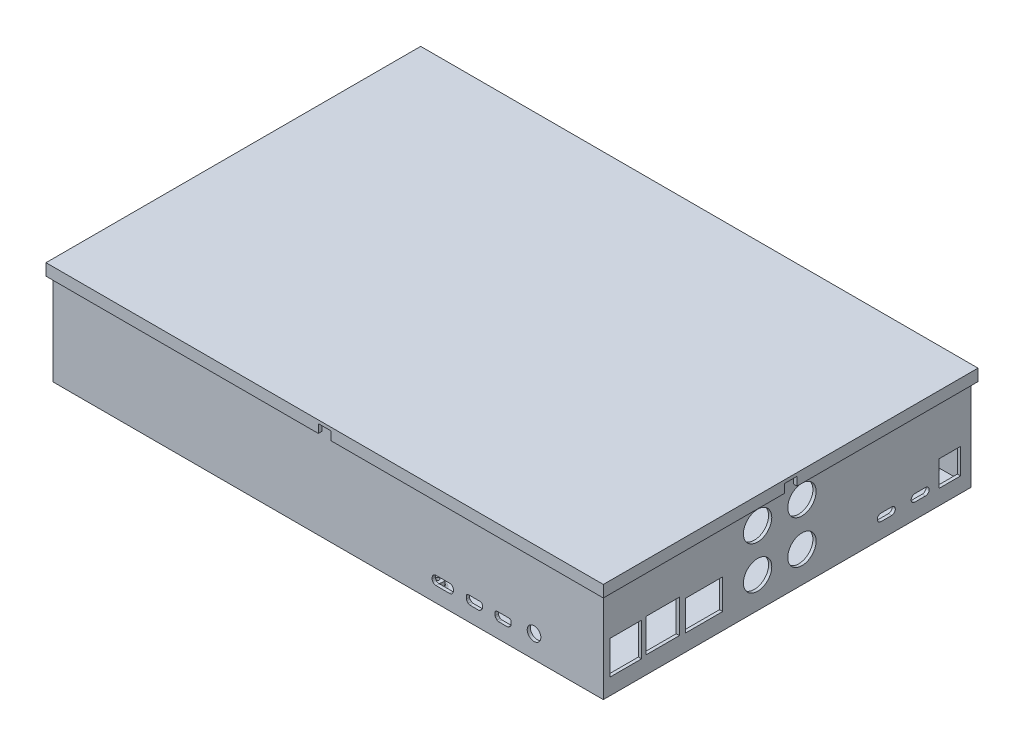
SolidWorks part; units mm, degrees
ref_plane "Front Plane" through (0, 0, 0) normal (0, 0, 1) x (1, 0, 0)
ref_plane "Top Plane" through (0, 0, 0) normal (0, 1, 0) x (1, 0, 0)
ref_plane "Right Plane" through (0, 0, 0) normal (1, 0, 0) x (0, 0, -1)
sketch "Sketch1" plane through (0, 0, 0) normal (0, -1, 0) x (1, 0, 0)
  line L0 (-24.0179, 95.5892) -> (-144.0179, 95.5892) construction
  line L1 (-174.0179, 95.5892) -> (80.9821, 95.5892)
  line L2 (-174.0179, 95.5892) -> (-174.0179, -73.7508)
  line L3 (-174.0179, -73.7508) -> (80.9821, -73.7508)
  line L4 (80.9821, 95.5892) -> (80.9821, -73.7508)
  line L5 (-24.0179, 95.5892) -> (-144.0179, 95.5892)
  line L6 (79.9821, -73.7508) -> (-17.0779, -73.7508) construction
  line L7 (79.9821, -73.7508) -> (-17.0779, -73.7508)
  line L8 (80.9821, -21.4108) -> (80.9821, -72.7508) construction
  line L9 (80.9821, -21.4108) -> (80.9821, -72.7508)
  line L10 (-144.0179, 95.5892) -> (-144.0179, 15.5892) construction
  line L11 (-144.0179, 95.5892) -> (-144.0179, 15.5892)
  dimension "D1" = 30
  dimension "D2" = 0
  dimension "D3" = 0
  dimension "D4" = 0
extrude "Boss-Extrude1" add sketch "Sketch1" along normal blind 2 from offset 4 contours L4 L3 L2 L1
sketch "Sketch2" plane through (0, -4, 0) normal (0, 1, 0) x (1, 0, 0)
  line L0 (-175.5179, 75.2508) -> (-175.5179, -97.0892)
  line L1 (-175.5179, -97.0892) -> (82.4821, -97.0892)
  line L2 (82.4821, -97.0892) -> (82.4821, 75.2508)
  line L3 (82.4821, 75.2508) -> (-175.5179, 75.2508)
  line L4 (-174.0179, -95.5892) -> (80.9821, -95.5892)
  line L5 (80.9821, -95.5892) -> (80.9821, 73.7508)
  line L6 (80.9821, 73.7508) -> (-174.0179, 73.7508)
  line L7 (-174.0179, 73.7508) -> (-174.0179, -95.5892)
  line L8 (-174.0179, -95.5892) -> (80.9821, -95.5892)
  line L9 (80.9821, -95.5892) -> (80.9821, 73.7508)
  line L10 (80.9821, 73.7508) -> (-174.0179, 73.7508)
  line L11 (-174.0179, 73.7508) -> (-174.0179, -95.5892)
  dimension "D1" = 0
  dimension "D2" = 1.5
extrude "Boss-Extrude2" add sketch "Sketch2" along normal blind 45 and the other way up to surface (2 mm away) other way up to face at (-46.5179, -6, 10.9192)
sketch "Sketch3" plane through (0, 0, 97.0892) normal (0, 0, 1) x (1, 0, 0)
  line L8 (4.0121, 1.1) -> (10.3521, 1.1)
  line L9 (12.1521, 2.9) -> (12.1521, 3.46)
  line L10 (10.3521, 5.26) -> (4.0121, 5.26)
  line L11 (2.2121, 3.46) -> (2.2121, 2.9)
  line L12 (4.0121, 1.1) -> (10.3521, 1.1)
  line L13 (12.1521, 2.9) -> (12.1521, 3.46)
  line L14 (10.3521, 5.26) -> (4.0121, 5.26)
  line L15 (2.2121, 3.46) -> (2.2121, 2.9)
  line L32 (21.8221, 1.1) -> (19.8266, 1.1)
  line L33 (19.1371, 1.3964) -> (18.4927, 2.0762)
  line L34 (18.2321, 2.7298) -> (18.2321, 4.05)
  line L35 (19.1821, 5) -> (24.7821, 5)
  line L36 (21.8221, 1.1) -> (19.8266, 1.1)
  line L37 (19.1371, 1.3964) -> (18.4927, 2.0762)
  line L38 (18.2321, 2.7298) -> (18.2321, 4.05)
  line L39 (19.1821, 5) -> (24.7821, 5)
  line L54 (22.1421, 1.1) -> (24.1376, 1.1)
  line L55 (24.827, 1.3964) -> (25.4715, 2.0762)
  line L56 (25.7321, 2.7298) -> (25.7321, 4.05)
  line L57 (22.1421, 1.1) -> (24.1376, 1.1)
  line L58 (24.827, 1.3964) -> (25.4715, 2.0762)
  line L59 (25.7321, 2.7298) -> (25.7321, 4.05)
  line L86 (35.6421, 1.1) -> (35.3221, 1.1)
  line L87 (39.2321, 4.05) -> (39.2321, 2.7298)
  line L88 (35.3221, 1.1) -> (33.3266, 1.1)
  line L89 (32.6371, 1.3964) -> (31.9927, 2.0762)
  line L90 (31.7321, 2.7298) -> (31.7321, 4.05)
  line L91 (32.6821, 5) -> (38.2821, 5)
  line L92 (39.2321, 4.05) -> (39.2321, 2.7298)
  line L93 (35.3221, 1.1) -> (33.3266, 1.1)
  line L94 (32.6371, 1.3964) -> (31.9927, 2.0762)
  line L95 (31.7321, 2.7298) -> (31.7321, 4.05)
  line L96 (32.6821, 5) -> (38.2821, 5)
  line L97 (22.1421, 1.1) -> (21.8221, 1.1)
  line L98 (35.6421, 1.1) -> (37.6376, 1.1)
  line L99 (38.327, 1.3964) -> (38.9715, 2.0762)
  line L100 (35.6421, 1.1) -> (37.6376, 1.1)
  line L101 (38.327, 1.3964) -> (38.9715, 2.0762)
  arc A8 (10.3521, 1.1) -> (12.1521, 2.9) centre (10.3521, 2.9) ccw
  arc A9 (12.1521, 3.46) -> (10.3521, 5.26) centre (10.3521, 3.46) ccw
  arc A10 (4.0121, 5.26) -> (2.2121, 3.46) centre (4.0121, 3.46) ccw
  arc A11 (2.2121, 2.9) -> (4.0121, 1.1) centre (4.0121, 2.9) ccw
  arc A12 (10.3521, 1.1) -> (12.1521, 2.9) centre (10.3521, 2.9) ccw
  arc A13 (12.1521, 3.46) -> (10.3521, 5.26) centre (10.3521, 3.46) ccw
  arc A14 (4.0121, 5.26) -> (2.2121, 3.46) centre (4.0121, 3.46) ccw
  arc A15 (2.2121, 2.9) -> (4.0121, 1.1) centre (4.0121, 2.9) ccw
  arc A27 (19.1371, 1.3964) -> (19.8266, 1.1) centre (19.8266, 2.05) ccw
  arc A28 (18.2321, 2.7298) -> (18.4927, 2.0762) centre (19.1821, 2.7298) ccw
  arc A29 (19.1821, 5) -> (18.2321, 4.05) centre (19.1821, 4.05) ccw
  arc A30 (19.1371, 1.3964) -> (19.8266, 1.1) centre (19.8266, 2.05) ccw
  arc A31 (18.2321, 2.7298) -> (18.4927, 2.0762) centre (19.1821, 2.7298) ccw
  arc A32 (19.1821, 5) -> (18.2321, 4.05) centre (19.1821, 4.05) ccw
  arc A53 (24.1376, 1.1) -> (24.827, 1.3964) centre (24.1376, 2.05) ccw
  arc A54 (25.4715, 2.0762) -> (25.7321, 2.7298) centre (24.7821, 2.7298) ccw
  arc A55 (25.7321, 4.05) -> (24.7821, 5) centre (24.7821, 4.05) ccw
  arc A56 (24.1376, 1.1) -> (24.827, 1.3964) centre (24.1376, 2.05) ccw
  arc A57 (25.4715, 2.0762) -> (25.7321, 2.7298) centre (24.7821, 2.7298) ccw
  arc A58 (25.7321, 4.05) -> (24.7821, 5) centre (24.7821, 4.05) ccw
  arc A80 (39.2321, 4.05) -> (38.2821, 5) centre (38.2821, 4.05) ccw
  arc A81 (32.6371, 1.3964) -> (33.3266, 1.1) centre (33.3266, 2.05) ccw
  arc A82 (31.7321, 2.7298) -> (31.9927, 2.0762) centre (32.6821, 2.7298) ccw
  arc A83 (32.6821, 5) -> (31.7321, 4.05) centre (32.6821, 4.05) ccw
  arc A84 (39.2321, 4.05) -> (38.2821, 5) centre (38.2821, 4.05) ccw
  arc A85 (32.6371, 1.3964) -> (33.3266, 1.1) centre (33.3266, 2.05) ccw
  arc A86 (31.7321, 2.7298) -> (31.9927, 2.0762) centre (32.6821, 2.7298) ccw
  arc A87 (32.6821, 5) -> (31.7321, 4.05) centre (32.6821, 4.05) ccw
  arc A92 (37.6376, 1.1) -> (38.327, 1.3964) centre (37.6376, 2.05) ccw
  arc A93 (38.9715, 2.0762) -> (39.2321, 2.7298) centre (38.2821, 2.7298) ccw
  arc A94 (37.6376, 1.1) -> (38.327, 1.3964) centre (37.6376, 2.05) ccw
  arc A95 (38.9715, 2.0762) -> (39.2321, 2.7298) centre (38.2821, 2.7298) ccw
  circle A96 centre (49.9821, 4.6) radius 3.2
  circle A97 centre (49.9821, 4.6) radius 3.2
  dimension "D1" = 0.5
  dimension "D2" = 0.5
  dimension "D3" = 0.5
  dimension "D4" = 0.5
  dimension "D5" = 0.5
  dimension "D6" = 0.5
extrude "Cut-Extrude1" cut sketch "Sketch3" against normal blind 30
sketch "Sketch4" plane through (82.4821, 0, 0) normal (1, 0, 0) x (0, 0, -1)
  line L0 (38.5008, 4.145) -> (32.8008, 4.145) construction
  line L1 (38.5008, 4.145) -> (32.8008, 4.145)
  line L2 (48.6758, 4.0894) -> (54.3758, 4.0894) construction
  line L3 (48.6758, 4.0894) -> (54.3758, 4.0894)
  line L4 (38.5008, 4.145) -> (48.6758, 4.0894)
  line L5 (43.5883, 4.1172) -> (43.5883, 5.0147)
  line L6 (35.6508, 4.145) -> (35.6508, 1.7159)
  line L7 (51.5258, 4.0894) -> (51.5258, 1.7512)
  line L8 (49.0258, 2.9203) -> (54.0258, 2.9203) construction
  line L9 (49.0258, 4.645) -> (54.0258, 4.645)
  line L10 (49.0258, 1.1956) -> (54.0258, 1.1956)
  line L11 (38.1508, 2.9203) -> (33.1508, 2.9203) construction
  line L12 (38.1508, 4.645) -> (33.1508, 4.645)
  line L13 (38.1508, 1.1956) -> (33.1508, 1.1956)
  line L22 (70.4488, 13.1) -> (60.4488, 13.1)
  line L23 (60.4488, 13.1) -> (60.4488, 1.1)
  line L24 (60.4488, 1.1) -> (70.4488, 1.1)
  line L25 (70.4488, 1.1) -> (70.4488, 13.1)
  line L26 (70.4488, 13.1) -> (60.4488, 13.1)
  line L27 (60.4488, 13.1) -> (60.4488, 1.1)
  line L28 (60.4488, 1.1) -> (70.4488, 1.1)
  line L29 (70.4488, 1.1) -> (70.4488, 13.1)
  arc A0 (49.0258, 4.645) -> (49.0258, 1.1956) centre (49.0258, 2.9203) ccw
  arc A1 (54.0258, 1.1956) -> (54.0258, 4.645) centre (54.0258, 2.9203) ccw
  arc A2 (38.1508, 4.645) -> (38.1508, 1.1956) centre (38.1508, 2.9203) cw
  arc A3 (33.1508, 1.1956) -> (33.1508, 4.645) centre (33.1508, 2.9203) cw
  point P12 (51.5258, 2.9203)
  point P19 (35.6508, 2.9203)
  dimension "D1" = 5
  dimension "D2" = 0.5
extrude "Cut-Extrude2" cut sketch "Sketch4" against normal blind 30 contours A3 L13 A2 L12 | L10 A1 L9 A0 | L28 L29 L26 L27 region at (82.4821, 4.4177, -48.3732) region at (82.4821, 2.2955, -39.66) region at (82.4821, 7.1, -65.4488)
sketch "Sketch5" plane through (82.4821, 0, 0) normal (1, 0, 0) x (0, 0, -1)
  line L8 (-76.9733, 17.8) -> (-61.4142, 17.8)
  line L9 (-76.9733, 17.8) -> (-76.9733, 2.18)
  line L10 (-58.5892, 15.9) -> (-58.5892, 1.8)
  line L11 (-41.0892, 15.9) -> (-58.5892, 15.9)
  line L12 (-41.0892, 1.8) -> (-41.0892, 15.9)
  line L13 (-58.5892, 15.9) -> (-58.5892, 1.8)
  line L14 (-41.0892, 15.9) -> (-58.5892, 15.9)
  line L15 (-41.0892, 1.8) -> (-41.0892, 15.9)
  line L16 (-76.9733, 2.18) -> (-61.4142, 2.18)
  line L17 (-61.4142, 17.8) -> (-61.4142, 2.18)
  line L18 (-68.5792, 2.18) -> (-63.3392, 2.18) construction
  line L19 (-63.3392, 17.8) -> (-73.8392, 17.8) construction
  line L20 (-94.0392, 11) -> (-94.0392, 8.6) construction
  line L21 (-94.0392, 17.32) -> (-79.1392, 17.32)
  line L22 (-94.0392, 17.32) -> (-94.0392, 1.6)
  line L23 (-94.0392, 1.6) -> (-79.1392, 1.6)
  line L24 (-79.1392, 17.32) -> (-79.1392, 1.6)
  line L26 (-94.0392, 7.3258) -> (-94.0392, 7.2852)
  line L28 (-94.5261, 7.3258) -> (-94.5261, 7.2852)
  line L29 (-79.1392, 11) -> (-79.1392, 8.6) construction
  line L30 (-92.5892, 1.6) -> (-42.5892, 1.6) construction
  line L31 (-83.8392, 17.32) -> (-86.5392, 17.32) construction
  line L32 (-41.0892, 1.8) -> (-58.5892, 1.8)
  arc A2 (-3.9298, 3.1042) -> (-3.9298, 13.9042) centre (-3.9298, 8.5042) ccw construction
  arc A3 (-3.9298, 3.1042) -> (-3.9298, 13.9042) centre (-3.9298, 8.5042) ccw
  arc A4 (-3.9298, 35.3458) -> (-3.9298, 22.0458) centre (-3.9298, 28.6958) ccw
  arc A5 (-3.9298, 22.0458) -> (-3.9298, 35.3458) centre (-3.9298, 28.6958) ccw
  arc A6 (-3.9298, 35.3458) -> (-3.9298, 22.0458) centre (-3.9298, 28.6958) ccw
  arc A7 (-3.9298, 22.0458) -> (-3.9298, 35.3458) centre (-3.9298, 28.6958) ccw
  arc A8 (-24.7298, 3.1042) -> (-24.7298, 13.9042) centre (-24.7298, 8.5042) ccw construction
  arc A9 (-24.7298, 3.1042) -> (-24.7298, 13.9042) centre (-24.7298, 8.5042) ccw
  circle A10 centre (-24.7298, 28.5042) radius 6.65
  circle A11 centre (-24.7298, 8.5042) radius 6.65
  circle A12 centre (-3.9298, 8.5042) radius 6.65
  spline S0 degree 3 poles (-711.4769, 4971.8053) (-337.5237, 1657.2751) (-108.2325, 7.3404) (-23.5785, 22.0054) (-23.5551, 22.0096) (-23.1608, 22.0825) (-22.8013, 22.1812) (-22.4001, 22.3289) (-22.3521, 22.3471) (-21.9895, 22.4907) (-21.6902, 22.6363) (-21.3063, 22.8605) (-21.2135, 22.9178) (-20.7371, 23.2292) (-20.3848, 23.5154) (-19.7811, 24.119) (-19.5272, 24.4235) (-19.2685, 24.7977) (-19.2361, 24.846) (-18.9769, 25.2424) (-18.7832, 25.6106) (-18.6139, 26.023) (-18.603, 26.05) (-18.4455, 26.4477) (-18.3328, 26.8309) (-18.2499, 27.2507) (-18.2445, 27.2785) (-18.1665, 27.6999) (-18.1298, 28.1009) (-18.1297, 28.8824) (-18.162, 29.2579) (-18.2309, 29.6555) (-18.2351, 29.6789) (-18.308, 30.0732) (-18.4067, 30.4328) (-18.5544, 30.8339) (-18.5727, 30.8819) (-18.7162, 31.2445) (-18.8618, 31.5439) (-19.086, 31.9277) (-19.1433, 32.0206) (-19.4547, 32.4969) (-19.741, 32.8492) (-20.3445, 33.4529) (-20.6491, 33.7069) (-21.0232, 33.9655) (-21.0716, 33.9979) (-21.4679, 34.2571) (-21.8361, 34.4508) (-22.2485, 34.6202) (-22.2755, 34.631) (-22.6732, 34.7885) (-23.0564, 34.9012) (-23.4762, 34.9842) (-23.504, 34.9895) (-76.1673, 44.7393) (-206.8261, -591.9511) (4537.529, -1875.475) knots -6.623505 -6.623505 -6.623505 -6.623505 0.029297 0.029297 0.03125 0.03125 0.058594 0.058594 0.0625 0.0625 0.085938 0.085938 0.09375 0.09375 0.125 0.125 0.152344 0.152344 0.15625 0.15625 0.185547 0.185547 0.1875 0.1875 0.216797 0.216797 0.21875 0.21875 0.25 0.25 0.279297 0.279297 0.28125 0.28125 0.308594 0.308594 0.3125 0.3125 0.335938 0.335938 0.34375 0.34375 0.375 0.375 0.402344 0.402344 0.40625 0.40625 0.435547 0.435547 0.4375 0.4375 0.466797 0.466797 0.46875 0.46875 4.61643 4.61643 4.61643 4.61643 weights 1 1 1 1 1 1 1 1 1 1 1 1 1 1 1 1 1 1 1 1 1 1 1 1 1 1 1 1 1 1 1 1 1 1 1 1 1 1 1 1 1 1 1 1 1 1 1 1 1 1 1 1 1 1 1 1 1 1 only from (-24.7298, 21.9042) to (-24.7298, 35.1042) construction
  spline S1 degree 3 poles (-24.7298, 21.9042) (-24.3515, 21.9042) (-23.976, 21.9365) (-23.5785, 22.0054) (-23.5551, 22.0096) (-23.1608, 22.0825) (-22.8013, 22.1812) (-22.4001, 22.3289) (-22.3521, 22.3471) (-21.9895, 22.4907) (-21.6902, 22.6363) (-21.3063, 22.8605) (-21.2135, 22.9178) (-20.7371, 23.2292) (-20.3848, 23.5154) (-19.7811, 24.119) (-19.5272, 24.4235) (-19.2685, 24.7977) (-19.2361, 24.846) (-18.9769, 25.2424) (-18.7832, 25.6106) (-18.6139, 26.023) (-18.603, 26.05) (-18.4455, 26.4477) (-18.3328, 26.8309) (-18.2499, 27.2507) (-18.2445, 27.2785) (-18.1665, 27.6999) (-18.1298, 28.1009) (-18.1297, 28.8824) (-18.162, 29.2579) (-18.2309, 29.6555) (-18.2351, 29.6789) (-18.308, 30.0732) (-18.4067, 30.4328) (-18.5544, 30.8339) (-18.5727, 30.8819) (-18.7162, 31.2445) (-18.8618, 31.5439) (-19.086, 31.9277) (-19.1433, 32.0206) (-19.4547, 32.4969) (-19.741, 32.8492) (-20.3445, 33.4529) (-20.6491, 33.7069) (-21.0232, 33.9655) (-21.0716, 33.9979) (-21.4679, 34.2571) (-21.8361, 34.4508) (-22.2485, 34.6202) (-22.2755, 34.631) (-22.6732, 34.7885) (-23.0564, 34.9012) (-23.4762, 34.9842) (-23.504, 34.9895) (-23.9254, 35.0675) (-24.3264, 35.1042) (-24.7298, 35.1042) knots 0 0 0 0 0.029297 0.029297 0.03125 0.03125 0.058594 0.058594 0.0625 0.0625 0.085938 0.085938 0.09375 0.09375 0.125 0.125 0.152344 0.152344 0.15625 0.15625 0.185547 0.185547 0.1875 0.1875 0.216797 0.216797 0.21875 0.21875 0.25 0.25 0.279297 0.279297 0.28125 0.28125 0.308594 0.308594 0.3125 0.3125 0.335938 0.335938 0.34375 0.34375 0.375 0.375 0.402344 0.402344 0.40625 0.40625 0.435547 0.435547 0.4375 0.4375 0.466797 0.466797 0.46875 0.46875 0.5 0.5 0.5 0.5 weights 1 1 1 1 1 1 1 1 1 1 1 1 1 1 1 1 1 1 1 1 1 1 1 1 1 1 1 1 1 1 1 1 1 1 1 1 1 1 1 1 1 1 1 1 1 1 1 1 1 1 1 1 1 1 1 1 1 1
  dimension "D2" = 6.65
  dimension "D1" = 0.5
  dimension "D3" = 1
extrude "Cut-Extrude4" cut sketch "Sketch5" against normal blind 30 contours A10 | A11 | A12 | A6 A7 | L32 L15 L14 L13 | L17 L8 L9 L16 | L24 L21 L22 L23 region at (82.4821, 9.99, 69.1938) region at (82.4821, 8.85, 49.8392) region at (82.4821, 9.46, 86.5892) region at (82.4821, 28.6958, 3.9298) region at (82.4821, 28.5042, 24.7298) region at (82.4821, 8.5042, 24.7298) region at (82.4821, 8.5042, 3.9298)
sketch "Sketch6" plane through (-174.0179, 0, 0) normal (1, 0, 0) x (0, 0, -1)
  line L0 (-54.3892, 12.7658) -> (-54.3892, 24.6258)
  line L1 (-28.353, 19.2474) -> (-28.861, 19.7554)
  line L2 (-25.813, 19.2474) -> (-26.321, 19.7554)
  line L3 (-13.059, 19.7554) -> (-12.551, 19.2474)
  line L4 (-15.091, 19.2474) -> (-15.599, 19.7554)
  line L5 (-12.551, 19.2474) -> (-12.551, 19.7554)
  line L6 (-12.551, 19.7554) -> (-13.059, 19.7554)
  line L7 (-13.059, 19.7554) -> (-13.059, 19.2474)
  line L8 (-13.059, 19.2474) -> (-12.551, 19.2474)
  line L9 (-12.551, 19.2474) -> (-12.551, 19.7554)
  line L10 (-12.551, 19.7554) -> (-13.059, 19.7554)
  line L11 (-13.059, 19.7554) -> (-13.059, 19.2474)
  line L12 (-13.059, 19.2474) -> (-12.551, 19.2474)
  line L13 (-15.599, 19.7554) -> (-15.599, 19.2474)
  line L14 (-15.599, 19.2474) -> (-15.091, 19.2474)
  line L15 (-15.091, 19.2474) -> (-15.091, 19.7554)
  line L16 (-15.091, 19.7554) -> (-15.599, 19.7554)
  line L17 (-15.599, 19.7554) -> (-15.599, 19.2474)
  line L18 (-15.599, 19.2474) -> (-15.091, 19.2474)
  line L19 (-15.091, 19.2474) -> (-15.091, 19.7554)
  line L20 (-15.091, 19.7554) -> (-15.599, 19.7554)
  line L21 (-25.813, 19.2474) -> (-25.813, 19.7554)
  line L22 (-25.813, 19.7554) -> (-26.321, 19.7554)
  line L23 (-26.321, 19.7554) -> (-26.321, 19.2474)
  line L24 (-26.321, 19.2474) -> (-25.813, 19.2474)
  line L25 (-25.813, 19.2474) -> (-25.813, 19.7554)
  line L26 (-25.813, 19.7554) -> (-26.321, 19.7554)
  line L27 (-26.321, 19.7554) -> (-26.321, 19.2474)
  line L28 (-26.321, 19.2474) -> (-25.813, 19.2474)
  line L29 (-28.861, 19.7554) -> (-28.861, 19.2474)
  line L30 (-28.861, 19.2474) -> (-28.353, 19.2474)
  line L31 (-28.353, 19.2474) -> (-28.353, 19.7554)
  line L32 (-28.353, 19.7554) -> (-28.861, 19.7554)
  line L33 (-28.861, 19.7554) -> (-28.861, 19.2474)
  line L34 (-28.861, 19.2474) -> (-28.353, 19.2474)
  line L35 (-28.353, 19.2474) -> (-28.353, 19.7554)
  line L36 (-28.353, 19.7554) -> (-28.861, 19.7554)
  circle A0 centre (-54.3892, 18.6958) radius 6.65
  circle A1 centre (-75.1892, 18.6958) radius 6.65
  arc A2 (-75.1892, 16.1958) -> (-75.1892, 21.1958) centre (-75.1892, 18.6958) ccw construction
  arc A3 (-75.1892, 16.1958) -> (-75.1892, 21.1958) centre (-75.1892, 18.6958) ccw
  circle A5 centre (51.6265, 20.5) radius 8.75 construction
  arc A6 (21.8151, 16.0167) -> (21.8555, 16.0118) centre (22.3777, 20.5) ccw
  arc A7 (-54.3892, 13.8458) -> (-54.3892, 23.5458) centre (-54.3892, 18.6958) ccw construction
  circle A8 centre (22.3777, 20.5) radius 6.6
  circle A10 centre (51.6265, 20.5) radius 8.75 construction
  circle A11 centre (22.3777, 20.5) radius 7.6 construction
  circle A12 centre (22.3777, 20.5) radius 7.6 construction
  arc A13 (-54.3892, 13.8458) -> (-54.3892, 23.5458) centre (-54.3892, 18.6958) ccw
  circle A14 centre (-75.1892, 18.6958) radius 6.65
  circle A15 centre (51.6265, 20.5) radius 7.75
  circle A16 centre (-26.067, 19.5014) radius 0.75
  circle A17 centre (-28.607, 19.5014) radius 0.75
  circle A18 centre (-15.345, 19.5014) radius 0.75
  circle A19 centre (-12.805, 19.5014) radius 0.75
  spline S1 degree 3 poles (-69.2251, 37.9448) (-68.8468, 37.9448) (-68.4713, 37.9125) (-68.0738, 37.8436) (-68.0504, 37.8394) (-67.6561, 37.7665) (-67.2966, 37.6679) (-66.8954, 37.5202) (-66.8474, 37.5019) (-66.4848, 37.3583) (-66.1854, 37.2128) (-65.8016, 36.9886) (-65.7087, 36.9312) (-65.2324, 36.6198) (-64.8801, 36.3336) (-64.2764, 35.73) (-64.0224, 35.4255) (-63.7638, 35.0513) (-63.7314, 35.003) (-63.4722, 34.6066) (-63.2785, 34.2384) (-63.1092, 33.826) (-63.0983, 33.799) (-62.9408, 33.4013) (-62.8281, 33.0181) (-62.7452, 32.5983) (-62.7398, 32.5705) (-62.6618, 32.1491) (-62.6251, 31.7481) (-62.625, 30.9666) (-62.6573, 30.5912) (-62.7262, 30.1935) (-62.7304, 30.1701) (-62.8033, 29.7758) (-62.902, 29.4163) (-63.0497, 29.0151) (-63.068, 28.9671) (-63.2115, 28.6045) (-63.3571, 28.3051) (-63.5813, 27.9213) (-63.6386, 27.8284) (-63.95, 27.3521) (-64.2363, 26.9998) (-64.8398, 26.3961) (-65.1444, 26.1421) (-65.5185, 25.8835) (-65.5668, 25.8511) (-65.9632, 25.5919) (-66.3314, 25.3982) (-66.7438, 25.2289) (-66.7708, 25.218) (-67.1685, 25.0605) (-67.5517, 24.9478) (-67.9715, 24.8649) (-67.9993, 24.8595) (-68.4207, 24.7815) (-68.8217, 24.7448) (-69.2251, 24.7448) knots 0 0 0 0 0.029297 0.029297 0.03125 0.03125 0.058594 0.058594 0.0625 0.0625 0.085938 0.085938 0.09375 0.09375 0.125 0.125 0.152344 0.152344 0.15625 0.15625 0.185547 0.185547 0.1875 0.1875 0.216797 0.216797 0.21875 0.21875 0.25 0.25 0.279297 0.279297 0.28125 0.28125 0.308594 0.308594 0.3125 0.3125 0.335938 0.335938 0.34375 0.34375 0.375 0.375 0.402344 0.402344 0.40625 0.40625 0.435547 0.435547 0.4375 0.4375 0.466797 0.466797 0.46875 0.46875 0.5 0.5 0.5 0.5 weights 1 1 1 1 1 1 1 1 1 1 1 1 1 1 1 1 1 1 1 1 1 1 1 1 1 1 1 1 1 1 1 1 1 1 1 1 1 1 1 1 1 1 1 1 1 1 1 1 1 1 1 1 1 1 1 1 1 1
  spline S3 degree 3 poles (-90.0251, 37.9448) (-89.6468, 37.9448) (-89.2713, 37.9125) (-88.8738, 37.8436) (-88.8504, 37.8394) (-88.4561, 37.7665) (-88.0966, 37.6679) (-87.6954, 37.5202) (-87.6474, 37.5019) (-87.2848, 37.3583) (-86.9854, 37.2128) (-86.6016, 36.9886) (-86.5087, 36.9312) (-86.0324, 36.6198) (-85.6801, 36.3336) (-85.0764, 35.73) (-84.8224, 35.4255) (-84.5638, 35.0513) (-84.5314, 35.003) (-84.2722, 34.6066) (-84.0785, 34.2384) (-83.9092, 33.826) (-83.8983, 33.799) (-83.7408, 33.4013) (-83.6281, 33.0181) (-83.5452, 32.5983) (-83.5398, 32.5705) (-83.4618, 32.1491) (-83.4251, 31.7481) (-83.425, 30.9666) (-83.4573, 30.5912) (-83.5262, 30.1935) (-83.5304, 30.1701) (-83.6033, 29.7758) (-83.702, 29.4163) (-83.8497, 29.0151) (-83.868, 28.9671) (-84.0115, 28.6045) (-84.1571, 28.3051) (-84.3813, 27.9213) (-84.4386, 27.8284) (-84.75, 27.3521) (-85.0363, 26.9998) (-85.6398, 26.3961) (-85.9444, 26.1421) (-86.3185, 25.8835) (-86.3668, 25.8511) (-86.7632, 25.5919) (-87.1314, 25.3982) (-87.5438, 25.2289) (-87.5708, 25.218) (-87.9685, 25.0605) (-88.3517, 24.9478) (-88.7715, 24.8649) (-88.7993, 24.8595) (-89.2207, 24.7815) (-89.6217, 24.7448) (-90.0251, 24.7448) knots 0 0 0 0 0.029297 0.029297 0.03125 0.03125 0.058594 0.058594 0.0625 0.0625 0.085938 0.085938 0.09375 0.09375 0.125 0.125 0.152344 0.152344 0.15625 0.15625 0.185547 0.185547 0.1875 0.1875 0.216797 0.216797 0.21875 0.21875 0.25 0.25 0.279297 0.279297 0.28125 0.28125 0.308594 0.308594 0.3125 0.3125 0.335938 0.335938 0.34375 0.34375 0.375 0.375 0.402344 0.402344 0.40625 0.40625 0.435547 0.435547 0.4375 0.4375 0.466797 0.466797 0.46875 0.46875 0.5 0.5 0.5 0.5 weights 1 1 1 1 1 1 1 1 1 1 1 1 1 1 1 1 1 1 1 1 1 1 1 1 1 1 1 1 1 1 1 1 1 1 1 1 1 1 1 1 1 1 1 1 1 1 1 1 1 1 1 1 1 1 1 1 1 1
  point P23 (-54.3892, 18.6958)
  dimension "D1" = 13.3
  dimension "D2" = 1
  dimension "D8" = 1.5
  dimension "D3" = 1
  dimension "D4" = 0
  dimension "D5" = 0
  dimension "D6" = 0
  dimension "D7" = 0
extrude "Cut-Extrude6" cut sketch "Sketch6" against normal blind 30 contours A15 | A8 | A0 A13 L0 | L0 A13 | A1 | L27 L28 L2 | L25 L26 L2 | A16 L28 L27 L26 L25 | A17 L36 L35 L34 L33 | L35 L36 L1 | L33 L34 L1 | A19 L12 L11 L10 L9 | L11 L12 L3 | L9 L10 L3 | A18 L20 L19 L18 L17 | L17 L18 L4 | L19 L20 L4 region at (-174.0179, 18.6958, 52.3308) region at (-174.0179, 19.4167, 28.6917) region at (-174.0179, 19.5861, 28.5223) region at (-174.0179, 19.4167, 26.1517) region at (-174.0179, 19.5861, 25.9823) region at (-174.0179, 19.5861, 12.7204) region at (-174.0179, 19.4167, 12.8897) region at (-174.0179, 19.4167, 15.4297) region at (-174.0179, 19.5861, 15.2604) region at (-174.0179, 18.6958, 55.135) region at (-174.0179, 18.6958, 75.1892) region at (-174.0179, 20.5, -22.3777) region at (-174.0179, 20.5, -51.6265) region at (-174.0179, 19.5014, 26.7958) region at (-174.0179, 19.5014, 29.3358) region at (-174.0179, 19.5014, 16.0738) region at (-174.0179, 19.5014, 13.5338)
sketch "Sketch7" plane through (0, -4, 0) normal (0, 1, 0) x (1, 0, 0)
  circle A0 centre (-29.0179, -20.5892) radius 1.6 construction
  circle A1 centre (-29.0179, -20.5892) radius 1.6 construction
  circle A2 centre (-29.0179, -90.5892) radius 1.6 construction
  circle A3 centre (-29.0179, -90.5892) radius 1.6 construction
  circle A4 centre (-139.0179, -90.5892) radius 1.6 construction
  circle A5 centre (-139.0179, -90.5892) radius 1.6 construction
  circle A6 centre (-139.0179, -20.5892) radius 1.6 construction
  circle A7 centre (-139.0179, -20.5892) radius 1.6 construction
  circle A8 centre (-97.6179, 32.5808) radius 2 construction
  circle A9 centre (-97.6179, 32.5808) radius 2 construction
  circle A10 centre (-97.6179, 61.5808) radius 2 construction
  circle A11 centre (-97.6179, 61.5808) radius 2 construction
  circle A12 centre (-43.6179, 61.5808) radius 2 construction
  circle A14 centre (-43.6179, 61.5808) radius 2 construction
  circle A24 centre (-0.5179, -43.0892) radius 1.35 construction
  circle A25 centre (-0.5179, -43.0892) radius 1.35 construction
  circle A26 centre (-0.5179, -92.0892) radius 1.35 construction
  circle A27 centre (-0.5179, -92.0892) radius 1.35 construction
  circle A28 centre (57.4821, -92.0892) radius 1.35 construction
  circle A29 centre (57.4821, -92.0892) radius 1.35 construction
  circle A30 centre (57.4821, -43.0892) radius 1.35 construction
  circle A31 centre (57.4821, -43.0892) radius 1.35 construction
  circle A32 centre (65.7421, 22.9508) radius 1.5998 construction
  circle A33 centre (67.0121, 71.2108) radius 1.5998 construction
  circle A34 centre (-15.5379, 71.2108) radius 1.5998 construction
  circle A35 centre (-9.2292, 22.9508) radius 1.5694 construction
  circle A36 centre (-43.6179, 32.5808) radius 1.2072 construction
  circle A37 centre (-29.0179, -90.5892) radius 0.9846
  circle A38 centre (-29.0179, -90.5892) radius 2.619
  circle A39 centre (-0.5179, -43.0892) radius 0.9846
  circle A40 centre (-0.5179, -43.0892) radius 2.619
  circle A41 centre (57.4821, -43.0892) radius 2.619
  circle A42 centre (57.4821, -43.0892) radius 0.9846
  circle A43 centre (65.7421, 22.9508) radius 0.9846
  circle A44 centre (65.7421, 22.9508) radius 2.619
  circle A45 centre (67.0121, 71.2108) radius 2.619
  circle A46 centre (67.0121, 71.2108) radius 0.9846
  circle A47 centre (-29.0179, -20.5892) radius 2.619
  circle A48 centre (-29.0179, -20.5892) radius 0.9846
  circle A49 centre (-9.2292, 22.9508) radius 2.619
  circle A50 centre (-9.2292, 22.9508) radius 0.9846
  circle A51 centre (-43.6179, 32.5808) radius 0.9846
  circle A52 centre (-43.6179, 32.5808) radius 2.619
  circle A53 centre (-43.6179, 61.5808) radius 2.619
  circle A54 centre (-43.6179, 61.5808) radius 0.9846
  circle A55 centre (-97.6179, 32.5808) radius 0.9846
  circle A56 centre (-97.6179, 32.5808) radius 2.619
  circle A57 centre (-97.6179, 61.5808) radius 0.9846
  circle A58 centre (-97.6179, 61.5808) radius 2.619
  circle A59 centre (-139.0179, -20.4747) radius 2.619
  circle A60 centre (-139.0179, -20.4747) radius 0.9846
  circle A61 centre (-139.0179, -90.5892) radius 2.619
  circle A62 centre (-139.0179, -90.5892) radius 0.9846
  circle A63 centre (-15.5379, 71.2108) radius 2.619
  circle A64 centre (-15.5379, 71.2108) radius 0.9846
  circle A65 centre (-0.5179, -92.0892) radius 0.9846
  circle A66 centre (-0.5179, -92.0892) radius 2.619
  circle A67 centre (57.4821, -92.0892) radius 0.9846
  circle A68 centre (57.4821, -92.0892) radius 2.619
  dimension "D1" = 1.9692
  dimension "D2" = 5.238
extrude "Boss-Extrude3" add sketch "Sketch7" along normal blind 3
fillet "Fillet1" radius 1 16 edges at (-29.0179, -4, 93.2082) (-43.6179, -1, -29.9618) (57.4821, -1, 45.7082) (-0.5179, -4, 45.7082) (-139.0179, -4, 93.2082) (-139.0179, -4, 23.0937) (65.7421, -4, -20.3318) (67.0121, -4, -68.5918) (-9.2292, -4, -20.3318) (-29.0179, -4, 23.2082) (-97.6179, -4, -58.9618) (-97.6179, -4, -29.9618) (-15.5379, -4, -68.5918) (-43.6179, -4, -58.9618) (57.4821, -4, 94.7082) (-0.5179, -4, 94.7082)
sketch "Sketch8" plane through (0, 41, 0) normal (0, 1, 0) x (1, 0, 0)
  line L0 (84.1821, 76.9508) -> (-177.2179, 76.9508)
  line L5 (82.4821, 75.2508) -> (-175.5179, 75.2508)
  line L6 (-175.5179, 75.2508) -> (-175.5179, -97.0892)
  line L7 (-175.5179, -97.0892) -> (82.4821, -97.0892)
  line L8 (82.4821, -97.0892) -> (82.4821, 75.2508)
  line L9 (82.4821, 75.2508) -> (-175.5179, 75.2508) construction
  line L10 (-175.5179, 75.2508) -> (-175.5179, -97.0892) construction
  line L11 (-175.5179, -97.0892) -> (82.4821, -97.0892) construction
  line L12 (82.4821, -97.0892) -> (82.4821, 75.2508) construction
  line L13 (-177.2179, 76.9508) -> (-177.2179, -98.7892)
  line L14 (-177.2179, -98.7892) -> (84.1821, -98.7892)
  line L15 (84.1821, -98.7892) -> (84.1821, 76.9508)
  line L16 (84.1821, -10.9192) -> (-177.2179, -10.9192) construction
  line L17 (84.1821, -7.9192) -> (-177.2179, -7.9192)
  line L18 (84.1821, -13.9192) -> (-177.2179, -13.9192)
  line L19 (-46.5179, -98.7892) -> (-46.5179, 76.9508) construction
  line L20 (-43.5179, -98.7892) -> (-43.5179, 76.9508)
  line L21 (-49.5179, -98.7892) -> (-49.5179, 76.9508)
  point P3 (0, 0)
  dimension "D1" = 0
  dimension "D4" = 3
  dimension "D5" = 3
  dimension "D6" = 3
  dimension "D7" = 3
extrude "Boss-Extrude4" add sketch "Sketch8" against normal blind 4 separate body contours L20 L14 L15 L18 | L20 L17 L15 L0 | L14 L21 L18 L13 | L21 L0 L13 L17 region at (82.6488, 41, -34.5158) region at (-51.0512, 41, -76.1008) region at (82.6488, 41, 56.3542) region at (-176.3679, 41, 15.4525)
sketch "Sketch9" plane through (0, 41, 0) normal (0, 1, 0) x (1, 0, 0)
  line L0 (-49.5179, 76.9508) -> (-177.2179, 76.9508) construction
  line L1 (-49.5179, 76.9508) -> (-177.2179, 76.9508)
  line L2 (-177.2179, 76.9508) -> (-177.2179, -7.9192) construction
  line L3 (-177.2179, 76.9508) -> (-177.2179, -7.9192)
  line L4 (-177.2179, -98.7892) -> (-177.2179, -7.9192)
  line L5 (-177.2179, -98.7892) -> (84.1821, -98.7892)
  line L6 (84.1821, -98.7892) -> (84.1821, 76.9508)
  line L7 (84.1821, 76.9508) -> (-49.5179, 76.9508)
extrude "Boss-Extrude5" add sketch "Sketch9" along normal blind 1.5
